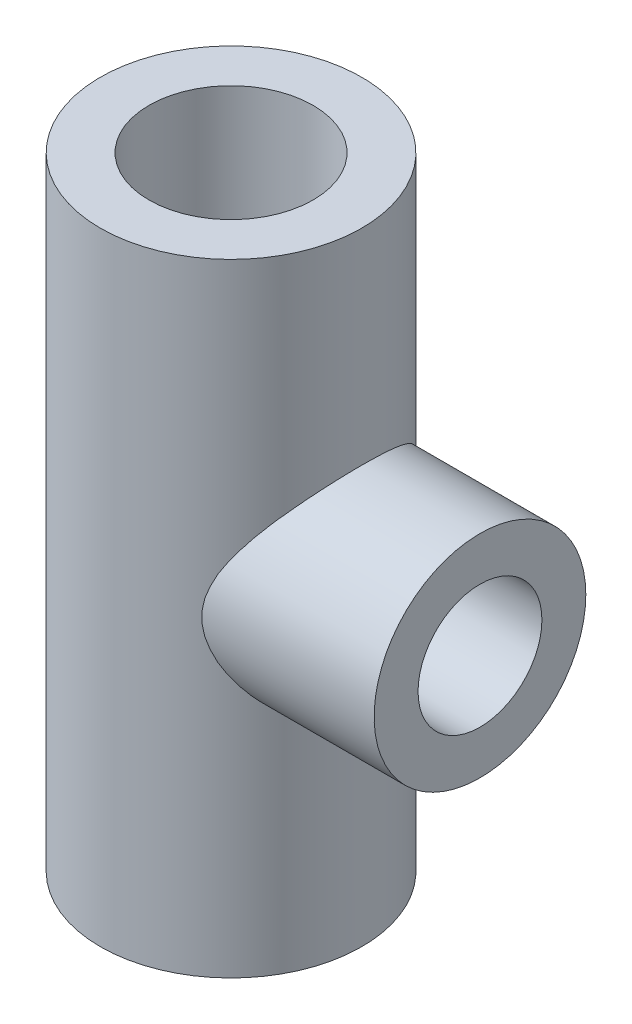
SolidWorks part; units mm, degrees
ref_plane "Front Plane" through (0, 0, 0) normal (0, 0, 1) x (1, 0, 0)
ref_plane "Top Plane" through (0, 0, 0) normal (0, 1, 0) x (1, 0, 0)
ref_plane "Right Plane" through (0, 0, 0) normal (1, 0, 0) x (0, 0, -1)
sketch "Sketch1" plane through (0, 0, 0) normal (0, 1, 0) x (1, 0, 0)
  circle A0 centre (0, 0) radius 16.6751
  circle A1 centre (0, 0) radius 10.4648
  dimension "D1" = 20.9296
  dimension "D2" = 33.3502
extrude "Boss-Extrude1" add sketch "Sketch1" along normal mid plane 79.375
sketch "Sketch2" plane through (0, 0, 0) normal (1, 0, 0) x (0, 0, -1)
  circle A0 centre (0, 0) radius 13.5001
  circle A1 centre (0, 0) radius 7.8994
  dimension "D1" = 27.0002
  dimension "D2" = 15.7988
ref_plane "Plane1" through (31.75, 0, 0) normal (1, 0, 0) x (0, 0, -1)
extrude "Boss-Extrude2" add sketch "Sketch2" along normal up to surface (31.75 mm away) separate body up to plane "Plane1"
sketch "Sketch4" plane through (31.75, 0, 0) normal (1, 0, 0) x (0, 0, -1)
  circle A0 centre (0, 0) radius 7.8994 construction
  circle A1 centre (0, 0) radius 7.8994
extrude "Cut-Extrude3" cut sketch "Sketch4" against normal up to surface (31.75 mm away) up to plane "Right Plane"
sketch "Sketch5" plane through (0, 39.6875, 0) normal (0, 1, 0) x (1, 0, 0)
  circle A0 centre (0, 0) radius 10.4648 construction
  circle A1 centre (0, 0) radius 10.4648
extrude "Cut-Extrude4" cut sketch "Sketch5" against normal up to surface (79.375 mm away) up to face at (0, -39.6875, 16.6751)
